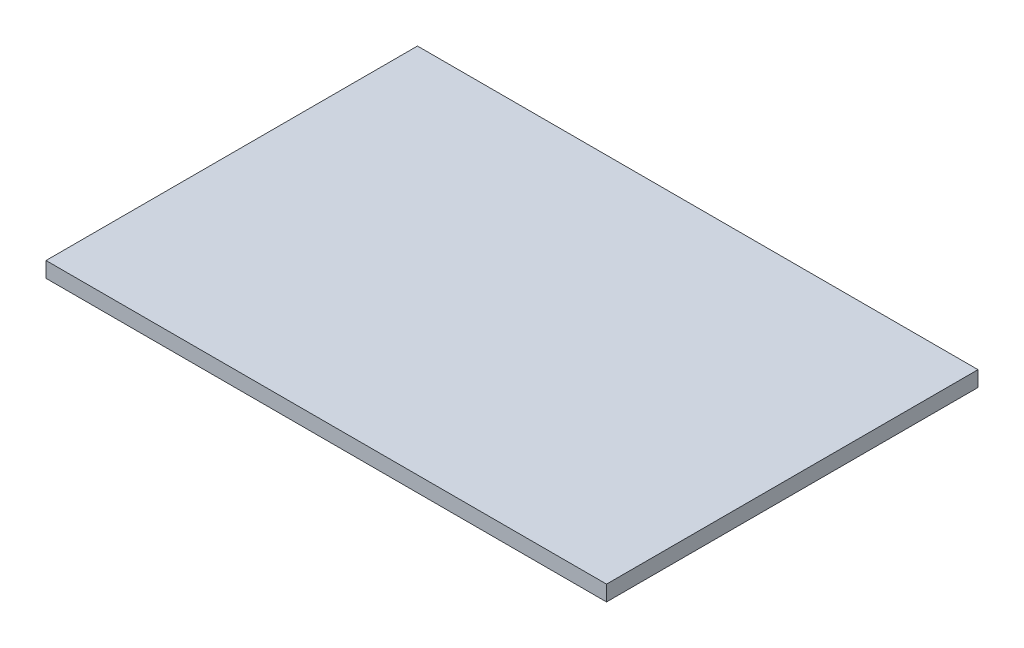
SolidWorks part; units mm, degrees
ref_plane "Front Plane" through (0, 0, 0) normal (0, 0, 1) x (1, 0, 0)
ref_plane "Top Plane" through (0, 0, 0) normal (0, 1, 0) x (1, 0, 0)
ref_plane "Right Plane" through (0, 0, 0) normal (1, 0, 0) x (0, 0, -1)
sketch "Sketch1" plane through (0, 0, 0) normal (0, 0, 1) x (1, 0, 0)
  line L0 (90.6195, -15.875) -> (90.6195, 155.575) construction
  line L1 (-139.3499, 155.575) -> (90.6195, 155.575)
  line L2 (-139.3499, 155.575) -> (-139.3499, 149.225)
  line L3 (-139.3499, 149.225) -> (90.6195, 149.225)
  line L4 (90.6195, 155.575) -> (90.6195, 149.225)
  dimension "D1" = 6.35
extrude "Boss-Extrude1" add sketch "Sketch1" along normal blind 152.4
